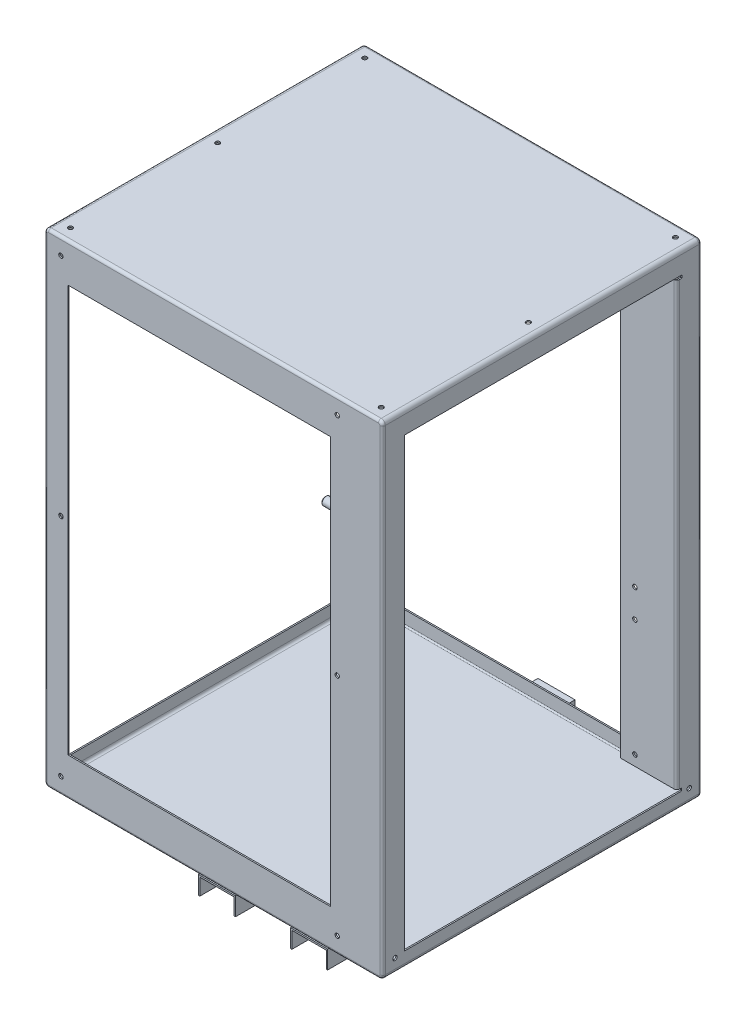
SolidWorks part; units mm, degrees
ref_plane "Спереди" through (0, 0, 0) normal (0, 0, 1) x (1, 0, 0)
ref_plane "Сверху" through (0, 0, 0) normal (0, 1, 0) x (1, 0, 0)
ref_plane "Справа" through (0, 0, 0) normal (1, 0, 0) x (0, 0, -1)
sketch "Эскиз1" plane through (0, 0, 0) normal (0, 0, 1) x (1, 0, 0)
  line L0 (-33.8044, 0) -> (37.3961, 0) construction
  line L1 (0, -31.1634) -> (0, 34.1213) construction
  line L3 (-120, -175) -> (120, -175)
  line L4 (-122, -173) -> (-122, 173)
  line L5 (-120, 175) -> (120, 175)
  line L6 (122, -173) -> (122, 173)
  arc A0 (-122, 173) -> (-120, 175) centre (-120, 173) cw
  arc A1 (120, 175) -> (122, 173) centre (120, 173) cw
  arc A2 (-120, -175) -> (-122, -173) centre (-120, -173) cw
  arc A3 (120, -175) -> (122, -173) centre (120, -173) ccw
  point P11 (-122, 175)
  point P14 (122, 175)
  point P17 (-122, -175)
  dimension "D3" = 2
  dimension "D1" = 350
  dimension "D2" = 244
extrude "Вытянуть-Тонкостенный1" add sketch "Эскиз1" along normal blind 232 thin thin type one direction wall 1
sketch "Эскиз2" plane through (123, 0, 0) normal (1, 0, 0) x (0, 0, -1)
  line L0 (-232, 176) -> (0, 176) construction
  line L1 (-216, -165) -> (-16, -165)
  line L2 (-216, -165) -> (-216, 160)
  line L3 (-216, 160) -> (-16, 160)
  line L4 (-16, -165) -> (-16, 160)
  line L5 (-116, 208.5566) -> (-116, -206.9252) construction
  line L6 (-232, -173) -> (-232, 173) construction
  line L7 (0, -173) -> (0, 173) construction
  dimension "D1" = 200
  dimension "D2" = 325
  dimension "D3" = 16
extrude "Вырез-Вытянуть1" cut sketch "Эскиз2" against normal blind 500
sketch "Эскиз3" plane through (0, 0, 232) normal (0, 0, 1) x (1, 0, 0)
  line L4 (-123, 173) -> (-123, -173)
  line L5 (-120, -176) -> (120, -176)
  line L6 (123, -173) -> (123, 173)
  line L7 (120, 176) -> (-120, 176)
  line L8 (-123, 173) -> (-123, -173)
  line L9 (-120, -176) -> (120, -176)
  line L10 (123, -173) -> (123, 173)
  line L11 (120, 176) -> (-120, 176)
  arc A4 (-120, 176) -> (-123, 173) centre (-120, 173) ccw
  arc A5 (-123, -173) -> (-120, -176) centre (-120, -173) ccw
  arc A6 (120, -176) -> (123, -173) centre (120, -173) ccw
  arc A7 (123, 173) -> (120, 176) centre (120, 173) ccw
  arc A8 (-120, 176) -> (-123, 173) centre (-120, 173) ccw
  arc A9 (-123, -173) -> (-120, -176) centre (-120, -173) ccw
  arc A10 (120, -176) -> (123, -173) centre (120, -173) ccw
  arc A11 (123, 173) -> (120, 176) centre (120, 173) ccw
  dimension "D1" = 0
extrude "Вытянуть1" add sketch "Эскиз3" against normal blind 1
sketch "Эскиз4" plane through (0, 0, 0) normal (0, 0, -1) x (-1, 0, 0)
  line L1 (0, 0) -> (0, 114.475) construction
  line L3 (-107, -165) -> (107, -165)
  line L4 (120, 176) -> (-120, 176)
  line L5 (-123, 173) -> (-123, -173)
  line L6 (-120, -176) -> (120, -176)
  line L7 (123, -173) -> (123, 173)
  line L8 (120, 176) -> (-120, 176)
  line L9 (-123, 173) -> (-123, -173)
  line L10 (-120, -176) -> (120, -176)
  line L11 (123, -173) -> (123, 173)
  line L12 (-107, -165) -> (-107, 160)
  line L13 (-107, 160) -> (107, 160)
  line L14 (107, -165) -> (107, 160)
  arc A4 (123, 173) -> (120, 176) centre (120, 173) ccw
  arc A5 (-120, 176) -> (-123, 173) centre (-120, 173) ccw
  arc A6 (-123, -173) -> (-120, -176) centre (-120, -173) ccw
  arc A7 (120, -176) -> (123, -173) centre (120, -173) ccw
  arc A8 (123, 173) -> (120, 176) centre (120, 173) ccw
  arc A9 (-120, 176) -> (-123, 173) centre (-120, 173) ccw
  arc A10 (-123, -173) -> (-120, -176) centre (-120, -173) ccw
  arc A11 (120, -176) -> (123, -173) centre (120, -173) ccw
  dimension "D2" = 214
  dimension "D3" = 325
  dimension "D4" = 16
  dimension "D1" = 0
extrude "Вытянуть2" add sketch "Эскиз4" against normal blind 1
fillet "Скругление1" radius 1 16 edges at (121.4142, 174.4142, 231) (122, 0, 231) (121.4142, -174.4142, 231) (0, -175, 231) (-121.4142, -174.4142, 231) (-122, 0, 231) (-121.4142, 174.4142, 231) (-121.4142, 174.4142, 1) (-122, 0, 1) (-121.4142, -174.4142, 1) (0, -175, 1) (121.4142, -174.4142, 1) (122, 0, 1) (121.4142, 174.4142, 1) (0, 175, 231) (0, 175, 1)
fillet "Скругление2" radius 2 16 edges at (-122.1213, 175.1213, 232) (0, 176, 232) (122.1213, 175.1213, 232) (123, 0, 232) (122.1213, -175.1213, 232) (0, -176, 232) (-122.1213, -175.1213, 232) (-122.1213, 175.1213, 0) (0, 176, 0) (122.1213, 175.1213, 0) (123, 0, 0) (122.1213, -175.1213, 0) (0, -176, 0) (-122.1213, -175.1213, 0) (-123, 0, 232) (-123, 0, 0)
sketch "Эскиз6" plane through (-123, 0, 0) normal (-1, 0, 0) x (0, 0, 1)
  line L0 (230, -176) -> (2, -176) construction
  line L1 (16, -165) -> (16, 160) construction
  circle A0 centre (8, -118) radius 3
  dimension "D1" = 6
  dimension "D3" = 8
  dimension "D2" = 58
extrude "Вытянуть3" add sketch "Эскиз6" along normal blind 20
chamfer "Фаска1" distance 1 angle 45 1 edges at (-143, -118, 11)
sketch "Эскиз7" plane through (-123, 0, 0) normal (-1, 0, 0) x (0, 0, 1)
  line L0 (9, -170.4186) -> (9, -81.3043) construction
  line L1 (230, -176) -> (2, -176) construction
  line L2 (0, -173) -> (0, 173) construction
  line L3 (116, 41.2045) -> (116, -219.7788) construction
  line L5 (230, 173) -> (2, 173) construction
  line L6 (16, -165) -> (16, 160) construction
  line L7 (216, 160) -> (216, -165) construction
  circle A0 centre (9, -95) radius 1.6
  circle A1 centre (9, -159) radius 1.6
  circle A2 centre (223, -95) radius 1.6
  circle A3 centre (223, -159) radius 1.6
  circle A4 centre (9, -80) radius 1.6
  circle A5 centre (223, -80) radius 1.6
  circle A6 centre (9, 168) radius 1.6
  circle A7 centre (223, 168) radius 1.6
  dimension "D4" = 3.2
  dimension "D7" = 5
  dimension "D8" = 3.2
  dimension "D1" = 17
  dimension "D2" = 81
  dimension "D3" = 9
  dimension "D5" = 96
  dimension "D6" = 9
extrude "Вырез-Вытянуть3" cut sketch "Эскиз7" against normal blind 20
sketch "Эскиз8" plane through (0, 0, 232) normal (0, 0, 1) x (1, 0, 0)
  line L0 (-123, -173) -> (-123, 173) construction
  line L1 (-106, -148) -> (85, -148)
  line L2 (-106, -148) -> (-106, 148)
  line L3 (-106, 148) -> (85, 148)
  line L4 (85, -148) -> (85, 148)
  line L5 (-120, 176) -> (120, 176) construction
  line L6 (120, -176) -> (-120, -176) construction
  line L7 (123, 173) -> (123, -173) construction
  dimension "D1" = 17
  dimension "D2" = 28
  dimension "D3" = 28
  dimension "D4" = 38
extrude "Вырез-Вытянуть4" cut sketch "Эскиз8" against normal blind 2
sketch "Эскиз9" plane through (0, 0, 232) normal (0, 0, 1) x (1, 0, 0)
  line L0 (-120, 176) -> (120, 176) construction
  line L1 (-123, -173) -> (-123, 173) construction
  line L2 (0, 0) -> (-174.4696, 0) construction
  line L3 (-10.5, 126.3418) -> (-10.5, -63.6186) construction
  line L4 (120, -176) -> (-120, -176) construction
  line L5 (-106, 148) -> (-106, -148) construction
  line L6 (85, -148) -> (85, 148) construction
  circle A0 centre (-111, 164) radius 1.6
  circle A1 centre (-111, 0) radius 1.6
  circle A2 centre (-111, -164) radius 1.6
  circle A3 centre (90, -164) radius 1.6
  circle A4 centre (90, 0) radius 1.6
  circle A5 centre (90, 164) radius 1.6
  dimension "D1" = 12
  dimension "D3" = 3.2
  dimension "D4" = 3.2
  dimension "D2" = 12
  dimension "D5" = 12
extrude "Вырез-Вытянуть5" cut sketch "Эскиз9" against normal blind 2
sketch "Эскиз10" plane through (123, 0, 0) normal (0, 0, 1) x (1, 0, 0)
  line L0 (-134, -176.0152) -> (-134, -175.8152)
  line L1 (-134, -189.0152) -> (-134, -176.0152)
  line L2 (-133, -189.0152) -> (-133, -177.0152)
  line L3 (-133, -177.0152) -> (-108, -177.0152)
  line L4 (-108, -189.0152) -> (-108, -177.0152)
  line L5 (-107, -175.8152) -> (-134, -175.8152)
  line L6 (-67, -176.0152) -> (-67, -175.8152)
  line L7 (-107, -189.0152) -> (-107, -176.0152)
  line L8 (-134, -189.0152) -> (-133, -189.0152)
  line L9 (-108, -189.0152) -> (-107, -189.0152)
  line L10 (-87, -139.0452) -> (-87, -213.9051) construction
  line L11 (-66, -189.0152) -> (-67, -189.0152)
  line L12 (-40, -189.0152) -> (-41, -189.0152)
  line L13 (-67, -189.0152) -> (-67, -176.0152)
  line L14 (-67, -175.8152) -> (-40, -175.8152)
  line L15 (-66, -189.0152) -> (-66, -177.0152)
  line L16 (-41, -177.0152) -> (-66, -177.0152)
  line L17 (-41, -189.0152) -> (-41, -177.0152)
  line L18 (-40, -189.0152) -> (-40, -176.0152)
  line L19 (-40, -176.0152) -> (-40, -175.8152)
  line L20 (0, 173) -> (0, -173) construction
  line L21 (-107, -176.0152) -> (-107, -175.8152)
  line L25 (-134, -176.0152) -> (-107, -176.0152) construction
  dimension "D1" = 40
  dimension "D2" = 12
  dimension "D3" = 25
  dimension "D4" = 12
  dimension "D6" = 20
  dimension "D5" = 1
extrude "Вытянуть6" add sketch "Эскиз10" along normal up to surface (232 mm away) and the other way blind 15 up to face at (88.4, 164, 232)
sketch "Эскиз16" plane through (0, 0, 16) normal (0, 0, 1) x (1, 0, 0)
  line L4 (122, 160) -> (122, -165)
  line L5 (122, -165) -> (123, -165)
  line L6 (123, -165) -> (123, 160)
  line L7 (123, 160) -> (122, 160)
  line L8 (122, 160) -> (122, -165)
  line L9 (122, -165) -> (123, -165)
  line L10 (123, -165) -> (123, 160)
  line L11 (123, 160) -> (122, 160)
  line L12 (-123, -165) -> (-122, -165)
  line L13 (-122, -165) -> (-122, 160)
  line L14 (-122, 160) -> (-123, 160)
  line L15 (-123, 160) -> (-123, -165)
  line L16 (-123, -165) -> (-122, -165)
  line L17 (-122, -165) -> (-122, 160)
  line L18 (-122, 160) -> (-123, 160)
  line L19 (-123, 160) -> (-123, -165)
  dimension "D1" = 0
  dimension "D2" = 0
extrude "Вытянуть9" add sketch "Эскиз16" along normal blind 2
sketch "Эскиз17" plane through (122, 0, 0) normal (-1, 0, 0) x (0, 0, 1)
  line L0 (18, 160) -> (18, -165) construction
  line L1 (18, -165) -> (216, -165) construction
  line L2 (18, -163) -> (17, -163)
  line L3 (18, -163) -> (18, 158)
  line L4 (18, 158) -> (17, 158)
  line L5 (17, -163) -> (17, 158)
  line L6 (216, 160) -> (18, 160) construction
  dimension "D1" = 1
  dimension "D2" = 2
  dimension "D3" = 2
extrude "Вытянуть10" add sketch "Эскиз17" along normal blind 40
sketch "Эскиз18" plane through (-122, 0, 0) normal (1, 0, 0) x (0, 0, -1)
  line L4 (-18, 158) -> (-18, -163)
  line L5 (-17, 158) -> (-18, 158)
  line L6 (-17, -163) -> (-17, 158)
  line L7 (-18, -163) -> (-17, -163)
  line L8 (-18, 158) -> (-18, -163)
  line L9 (-17, 158) -> (-18, 158)
  line L10 (-17, -163) -> (-17, 158)
  line L11 (-18, -163) -> (-17, -163)
  dimension "D1" = 0
extrude "Вытянуть11" add sketch "Эскиз18" along normal blind 40
sketch "Эскиз19" plane through (-122, 0, 0) normal (1, 0, 0) x (0, 0, -1)
  line L1 (-18, -165) -> (-14.5, -165)
  line L2 (-18, -165) -> (-18, -163)
  line L3 (-18, -163) -> (-14.5, -163)
  line L4 (-14.5, -165) -> (-14.5, -163)
  line L5 (-18, 160) -> (-14.5, 160)
  line L6 (-18, 160) -> (-18, 158)
  line L7 (-18, 158) -> (-14.5, 158)
  line L8 (-14.5, 160) -> (-14.5, 158)
  dimension "D1" = 3.5
  dimension "D2" = 2
  dimension "D3" = 2
  dimension "D4" = 3.5
extrude "Вырез-Вытянуть8" cut sketch "Эскиз19" against normal blind 40
sketch "Эскиз20" plane through (0, 0, 17) normal (0, 0, -1) x (-1, 0, 0)
  line L0 (0, 0) -> (0, 229.3247) construction
  line L1 (-92.5, 145.5) -> (-92.5, -135.839) construction
  line L2 (-120, 176) -> (120, 176) construction
  circle A0 centre (-92.5, 145.5) radius 1.6
  circle A1 centre (-92.5, -50) radius 1.6
  circle A2 centre (-92.5, -155.5) radius 1.6
  circle A3 centre (92.5, -155.5) radius 1.6
  circle A4 centre (92.5, -50) radius 1.6
  circle A5 centre (92.5, 145.5) radius 1.6
  circle A6 centre (-92.5, -70.5) radius 1.6
  circle A7 centre (92.5, -70.5) radius 1.6
  dimension "D1" = 301
  dimension "D3" = 30.5
  dimension "D4" = 3.2
  dimension "D5" = 195.5
  dimension "D6" = 85
  dimension "D2" = 92.5
extrude "Вырез-Вытянуть9" cut sketch "Эскиз20" against normal blind 10
fillet "Скругление4" radius 2 3 edges at (123, -2.5, 18) (-123, -2.5, 18) (-122, -2.5, 216)
sketch "Эскиз22" plane through (122, 0, 0) normal (-1, 0, 0) x (0, 0, 1)
  line L1 (14.5, -165) -> (19.251, -165)
  line L2 (14.5, -165) -> (14.5, -162.9892)
  line L3 (14.5, -162.9892) -> (19.251, -162.9892)
  line L4 (19.251, -165) -> (19.251, -162.9892)
  line L5 (17.7321, 160) -> (14.2321, 160)
  line L6 (17.7321, 160) -> (17.7321, 158)
  line L7 (17.7321, 158) -> (14.2321, 158)
  line L8 (14.2321, 160) -> (14.2321, 158)
  dimension "D1" = 2
  dimension "D2" = 3.5
extrude "Вырез-Вытянуть11" cut sketch "Эскиз22" against normal blind 10
sketch "Эскиз23" plane through (0, 176, 0) normal (0, 1, 0) x (1, 0, 0)
  line L0 (-123, -230) -> (-123, -2) construction
  line L1 (120, -232) -> (-120, -232) construction
  line L2 (-113, -223) -> (-113, -67.0841) construction
  line L3 (0, 0) -> (0, -260.3365) construction
  line L4 (123, -230) -> (123, -2) construction
  circle A0 centre (-113, -223) radius 1.6
  circle A1 centre (-113, -116) radius 1.6
  circle A2 centre (-113, -9) radius 1.6
  circle A3 centre (113, -223) radius 1.6
  circle A4 centre (113, -116) radius 1.6
  circle A5 centre (113, -9) radius 1.6
  dimension "D3" = 3.2
  dimension "D4" = 214
  dimension "D5" = 107
  dimension "D1" = 10
  dimension "D2" = 9
extrude "Вырез-Вытянуть12" cut sketch "Эскиз23" against normal blind 10
sketch "Эскиз24" plane through (123, 0, 0) normal (1, 0, 0) x (0, 0, -1)
  line L0 (-232, -173) -> (-232, 173) construction
  line L1 (-223, -166) -> (-9, -166) construction
  line L2 (-2, -176) -> (-230, -176) construction
  circle A1 centre (-9, -166) radius 1.6
  circle A3 centre (-223, -166) radius 1.6
  dimension "D1" = 214
  dimension "D2" = 3.2
  dimension "D3" = 3.2
  dimension "D4" = 9
  dimension "D5" = 10
extrude "Вырез-Вытянуть13" cut sketch "Эскиз24" against normal blind 10
